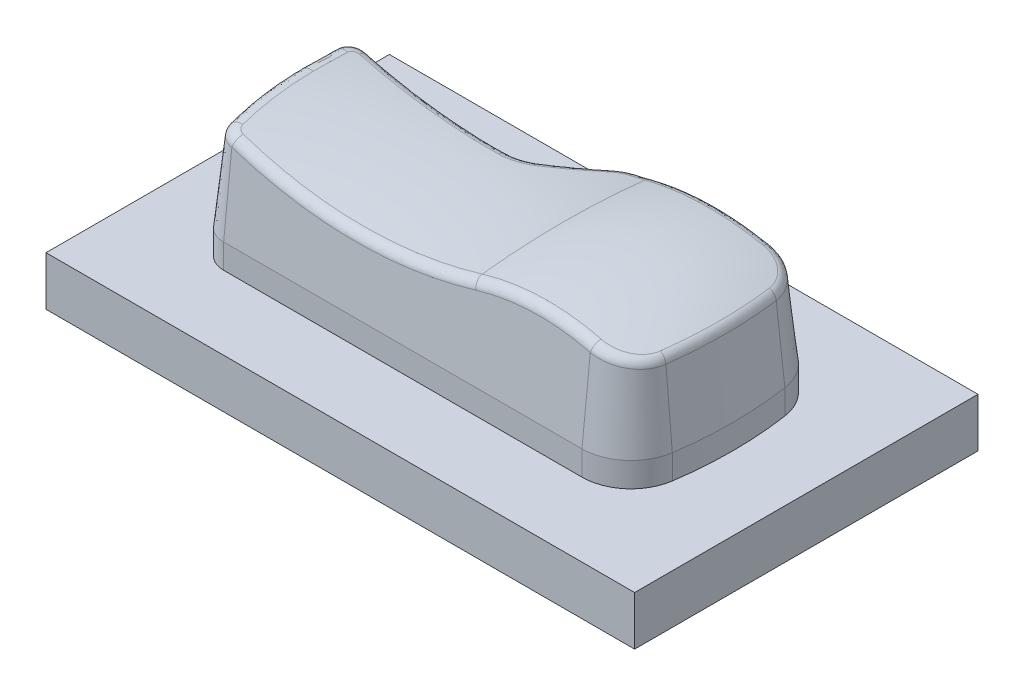
SolidWorks part; units mm, degrees
ref_plane "정면" through (0, 0, 0) normal (0, 0, 1) x (1, 0, 0)
ref_plane "윗면" through (0, 0, 0) normal (0, 1, 0) x (1, 0, 0)
ref_plane "우측면" through (0, 0, 0) normal (1, 0, 0) x (0, 0, -1)
sketch "스케치1" plane through (0, 0, 0) normal (0, 1, 0) x (1, 0, 0)
  line L1 (-60, 35) -> (60, 35)
  line L2 (-60, 35) -> (-60, -35)
  line L3 (-60, -35) -> (60, -35)
  line L4 (60, 35) -> (60, -35)
  line L5 (-60, 35) -> (60, -35) construction
  line L6 (-60, -35) -> (60, 35) construction
  point P0 (0, 0)
  dimension "D1" = 120
  dimension "D2" = 70
extrude "보스-돌출1" add sketch "스케치1" along normal blind 10
sketch "스케치3" plane through (0, 10, 0) normal (0, 1, 0) x (1, 0, 0)
  line L0 (-45, 7) -> (-45, 0)
  line L1 (-60, 35) -> (-60, -35) construction
  line L2 (-40, 12) -> (-11.5359, 12)
  line L3 (-6.5359, 13.3397) -> (2.6795, 18.6603)
  line L4 (7.6795, 20) -> (22, 20)
  line L5 (22, 20) -> (34.2607, 20)
  line L6 (-38.7824, -20) -> (34.2607, -20)
  line L7 (45, 58.8174) -> (45, -36.9445) construction
  arc A0 (-45, 0) -> (-43.7169, -15.8065) centre (53, 0) ccw
  arc A1 (44.152, 11.4706) -> (44.152, -11.4706) centre (-33, 0) cw
  arc A2 (-38.7824, -20) -> (-43.7169, -15.8065) centre (-38.7824, -15) cw
  arc A3 (-45, 7) -> (-40, 12) centre (-40, 7) cw
  arc A4 (34.2607, -20) -> (44.152, -11.4706) centre (34.2607, -10) ccw
  arc A5 (44.152, 11.4706) -> (34.2607, 20) centre (34.2607, 10) ccw
  arc A6 (7.6795, 20) -> (2.6795, 18.6603) centre (7.6795, 10) ccw
  arc A7 (-6.5359, 13.3397) -> (-11.5359, 12) centre (-11.5359, 22) cw
  point P15 (0, 0)
  point P16 (-3.0754, 20)
  point P21 (-45, 12)
  point P24 (42.3923, -20)
  point P27 (42.3923, 20)
  point P30 (5, 20)
  dimension "D1" = 98
  dimension "D4" = 78
  dimension "D11" = 5
  dimension "D12" = 10
  dimension "D13" = 10
  dimension "D2" = 15
  dimension "D3" = 12
  dimension "D5" = 40
  dimension "D6" = 90
  dimension "D7" = 150
  dimension "D8" = 17
  dimension "D9" = 20
  dimension "D10" = 82
extrude "보스-돌출4" add sketch "스케치3" along normal blind 5
sketch "스케치6" plane through (0, 15, 0) normal (0, 1, 0) x (1, 0, 0)
  line L5 (-38.7824, -20) -> (34.2607, -20)
  line L6 (34.2607, 20) -> (7.6795, 20)
  line L7 (2.6795, 18.6603) -> (-6.5359, 13.3397)
  line L8 (-11.5359, 12) -> (-40, 12)
  line L9 (-45, 7) -> (-45, 0)
  line L10 (-38.7824, -20) -> (34.2607, -20)
  line L11 (34.2607, 20) -> (7.6795, 20)
  line L12 (2.6795, 18.6603) -> (-6.5359, 13.3397)
  line L13 (-11.5359, 12) -> (-40, 12)
  line L14 (-45, 7) -> (-45, 0)
  arc A8 (-45, 0) -> (-43.7169, -15.8065) centre (53, 0) ccw
  arc A9 (-43.7169, -15.8065) -> (-38.7824, -20) centre (-38.7824, -15) ccw
  arc A10 (34.2607, -20) -> (44.152, -11.4706) centre (34.2607, -10) ccw
  arc A11 (44.152, -11.4706) -> (44.152, 11.4706) centre (-33, 0) ccw
  arc A12 (44.152, 11.4706) -> (34.2607, 20) centre (34.2607, 10) ccw
  arc A13 (7.6795, 20) -> (2.6795, 18.6603) centre (7.6795, 10) ccw
  arc A14 (-11.5359, 12) -> (-6.5359, 13.3397) centre (-11.5359, 22) ccw
  arc A15 (-40, 12) -> (-45, 7) centre (-40, 7) ccw
  arc A16 (-45, 0) -> (-43.7169, -15.8065) centre (53, 0) ccw
  arc A17 (-43.7169, -15.8065) -> (-38.7824, -20) centre (-38.7824, -15) ccw
  arc A18 (34.2607, -20) -> (44.152, -11.4706) centre (34.2607, -10) ccw
  arc A19 (44.152, -11.4706) -> (44.152, 11.4706) centre (-33, 0) ccw
  arc A20 (44.152, 11.4706) -> (34.2607, 20) centre (34.2607, 10) ccw
  arc A21 (7.6795, 20) -> (2.6795, 18.6603) centre (7.6795, 10) ccw
  arc A22 (-11.5359, 12) -> (-6.5359, 13.3397) centre (-11.5359, 22) ccw
  arc A23 (-40, 12) -> (-45, 7) centre (-40, 7) ccw
  dimension "D1" = 0
extrude "보스-돌출7" add sketch "스케치6" along normal blind 20 draft 6
sketch "스케치10" plane through (0, 0, 0) normal (1, 0, 0) x (0, 0, -1)
  line L3 (11.1615, 35) -> (-11.1615, 35) construction
  arc A0 (-20, 33.6607) -> (20, 33.6607) centre (0, -115) cw
  point P5 (0, 0)
  point P6 (0, 0)
  dimension "D1" = 150
  dimension "D2" = 20
  dimension "D3" = 33.6607
sketch "스케치11" plane through (0, 0, 0) normal (0, 0, 1) x (1, 0, 0)
  line L0 (-64.9303, 30) -> (82.499, 30) construction
  line L1 (-60, 0) -> (60, 0) construction
  line L3 (-4.1579, 35) -> (60.5469, 35) construction
  line L5 (-50, 37.8149) -> (-50, 40)
  line L6 (-50, 40) -> (50, 40)
  line L7 (50, 40) -> (50, 27.5634)
  line L8 (-38.7824, 35) -> (34.2607, 35) construction
  arc A0 (-50, 37.8149) -> (10.5203, 33.2143) centre (-13.3175, 120) ccw
  arc A1 (10.5203, 33.2143) -> (50, 27.5634) centre (23.7635, -15) cw
  point P10 (0, 0)
  dimension "D2" = 50
  dimension "D4" = 90
  dimension "D1" = 30
  dimension "D3" = 35
  dimension "D5" = 5
  dimension "D6" = 5
  dimension "D7" = 5
  dimension "D8" = 17.5634
sweep "컷-스윕2" cut profiles "스케치11" path "스케치10"
fillet "필렛1" radius 2 15 edges at (17.898, 33.5624, 18.049) (40.252, 31.3618, 15.7156) (39.5203, 31.5407, -16.371) (26.8098, 33.8199, -18.022) (5.2765, 30.8373, -17.9815) (-7.7009, 29.7501, -11.1049) (-42.3229, 34.5427, -8.8118) (-40.7747, 33.2793, 17.3472) (-18.8122, 28.9803, 18.5306)
